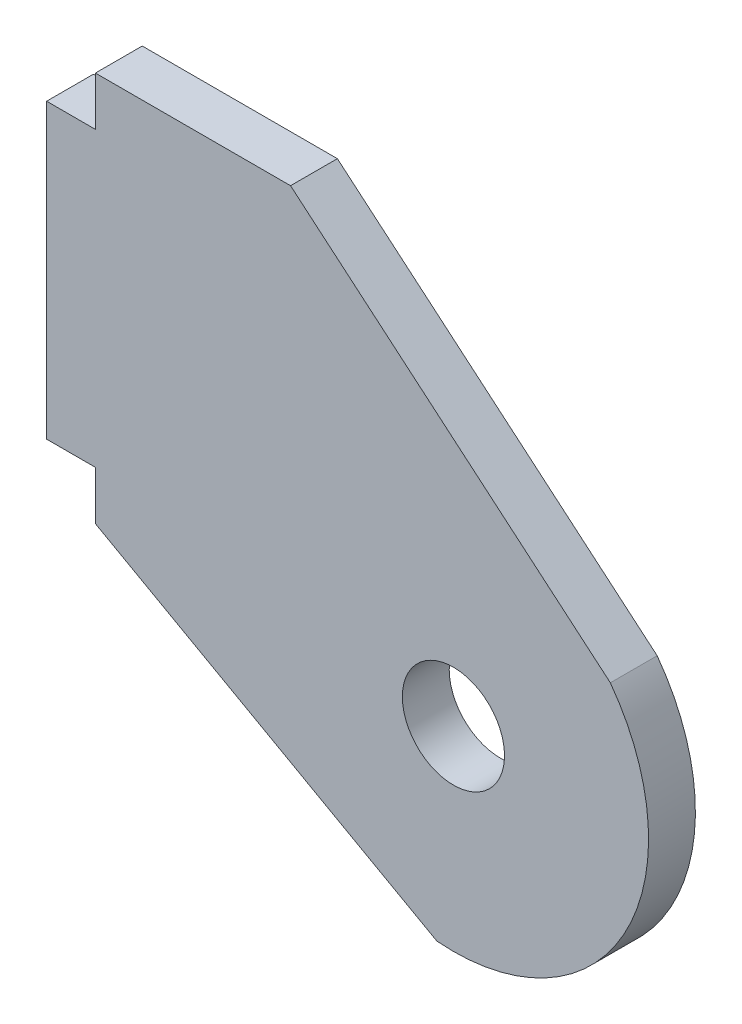
SolidWorks part; units mm, degrees
material "AISI 4130 Steel, normalized at 870C"
ref_plane "X-Y Datum" through (0, 0, 0) normal (0, 0, 1) x (1, 0, 0)
ref_plane "X-Z Datum" through (0, 0, 0) normal (0, 1, 0) x (1, 0, 0)
ref_plane "Y-Z Datum" through (0, 0, 0) normal (1, 0, 0) x (0, 0, -1)
sketch "Sketch1" plane through (0, 0, 0) normal (0, 0, 1) x (1, 0, 0)
  line L0 (427.9194, 0) -> (440.6194, 0)
  line L2 (427.9194, 0) -> (427.9194, -3.175)
  line L9 (427.9194, -25.4) -> (450.1444, -37.8155)
  line L10 (450.1444, -37.8155) -> (461.4322, -17.6092) construction
  line L12 (440.6194, 0) -> (461.4322, -17.6092)
  line L13 (427.9194, -22.225) -> (424.7444, -22.225)
  line L14 (424.7444, -22.225) -> (424.7444, -3.175)
  line L15 (424.7444, -3.175) -> (427.9194, -3.175)
  line L16 (427.9194, -22.225) -> (427.9194, -25.4)
  arc A0 (450.1444, -37.8155) -> (461.4322, -17.6092) centre (451.2216, -25.1613) ccw
  circle A1 centre (451.2216, -25.1613) radius 3.3236
  dimension "D2" = 22.225
  dimension "D3" = 12.7
  dimension "D1" = 12.7
  dimension "D4" = 3.175
  dimension "D5" = 19.05
  dimension "D6" = 26.4772
  dimension "D7" = 25.4577
  dimension "D8" = 27.2627
extrude "Boss-Extrude1" add sketch "Sketch1" along normal blind 3.048
